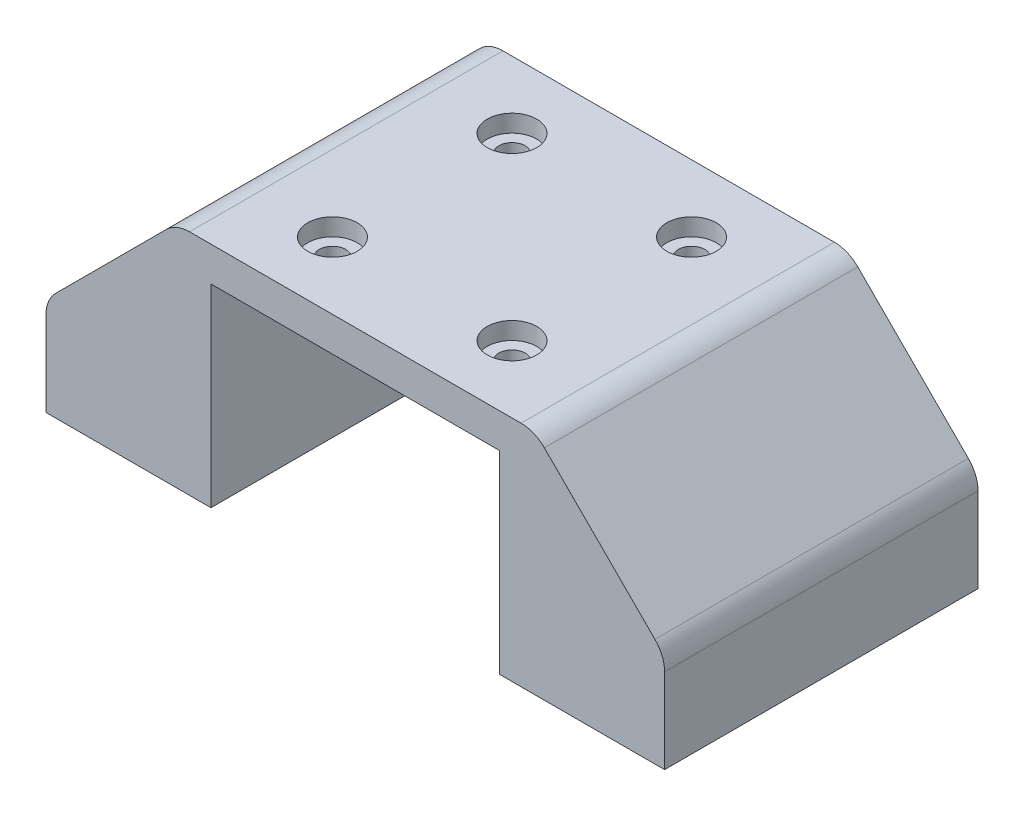
SolidWorks part; units mm, degrees
ref_plane "Front Plane" through (0, 0, 0) normal (0, 0, 1) x (1, 0, 0)
ref_plane "Top Plane" through (0, 0, 0) normal (0, 1, 0) x (1, 0, 0)
ref_plane "Right Plane" through (0, 0, 0) normal (1, 0, 0) x (0, 0, -1)
sketch "Sketch1" plane through (0, 0, 0) normal (0, 0, 1) x (1, 0, 0)
  line L0 (0, -12.67) -> (0, 30.502) construction
  line L1 (-11.1125, 0) -> (-11.1125, 14.9225)
  line L2 (-11.1125, 0) -> (-23.8125, 0)
  line L3 (-11.1125, 14.9225) -> (11.1125, 14.9225)
  line L4 (-23.8125, 17.5746) -> (23.8125, 17.5746)
  line L5 (-23.8125, 0) -> (-23.8125, 17.5746)
  line L6 (11.1125, 0) -> (23.8125, 0)
  line L7 (23.8125, 0) -> (23.8125, 17.5746)
  line L8 (11.1125, 0) -> (11.1125, 14.9225)
  point P9 (0, 17.5746)
  point P13 (0, 14.9225)
  dimension "D1" = 12.7
  dimension "D2" = 11.1125
  dimension "D3" = 14.9225
  dimension "D4" = 17.5746
extrude "Boss-Extrude1" add sketch "Sketch1" along normal blind 24.13
chamfer "Chamfer1" distance 10 angle 45 2 edges at (23.8125, 17.5746, 12.065) (-23.8125, 17.5746, 12.065)
fillet "Fillet1" radius 2.54 2 edges at (13.8125, 17.5746, 12.065) (-13.8125, 17.5746, 12.065)
fillet "Fillet2" radius 2.54 2 edges at (23.8125, 7.5746, 12.065) (-23.8125, 7.5746, 12.065)
sketch "Sketch2" plane through (0, 0, 0) normal (0, -1, 0) x (1, 0, 0)
  line L0 (0, -12.2519) -> (0, 31.6273) construction
  line L1 (-35.4754, 12.065) -> (35.4754, 12.065) construction
  line L2 (-11.1125, 0) -> (11.1125, 0) construction
  circle A0 centre (-19.05, 19.685) radius 2.032
  circle A1 centre (19.05, 19.685) radius 2.032
  circle A2 centre (19.05, 4.445) radius 2.032
  circle A3 centre (-19.05, 4.445) radius 2.032
  dimension "D1" = 4.064
  dimension "D2" = 7.62
  dimension "D3" = 12.065
  dimension "D4" = 19.05
extrude "Cut-Extrude1" cut sketch "Sketch2" against normal blind 10.16
sketch "Sketch3" plane through (0, 17.5746, 0) normal (0, 1, 0) x (1, 0, 0)
  line L0 (0, 9.1955) -> (0, -28.8887) construction
  line L1 (-14.5564, -12.065) -> (14.5564, -12.065) construction
  line L2 (-14.5564, -24.13) -> (-14.5564, 0) construction
  line L3 (14.5564, 0) -> (14.5564, -24.13) construction
  circle A0 centre (-6.9113, -5.1537) radius 1.016
  circle A1 centre (6.9113, -5.1537) radius 1.016
  circle A2 centre (6.9113, -18.9763) radius 1.016
  circle A3 centre (-6.9113, -18.9763) radius 1.016
  dimension "D3" = 2.032
  dimension "D1" = 6.9113
  dimension "D2" = 6.9113
extrude "Cut-Extrude2" cut sketch "Sketch3" against normal through all
sketch "Sketch4" plane through (0, 17.5746, 0) normal (0, 1, 0) x (1, 0, 0)
  line L0 (0, 10.8653) -> (0, -31.1365) construction
  line L1 (-14.5564, -12.065) -> (14.5564, -12.065) construction
  line L2 (-14.5564, -24.13) -> (-14.5564, 0) construction
  line L3 (14.5564, 0) -> (14.5564, -24.13) construction
  circle A0 centre (-6.9113, -5.1537) radius 1.905
  circle A1 centre (6.9113, -5.1537) radius 1.905
  circle A2 centre (6.9113, -18.9763) radius 1.905
  circle A3 centre (-6.9113, -18.9763) radius 1.905
  dimension "D1" = 3.81
extrude "Cut-Extrude3" cut sketch "Sketch4" against normal blind 1.3335
